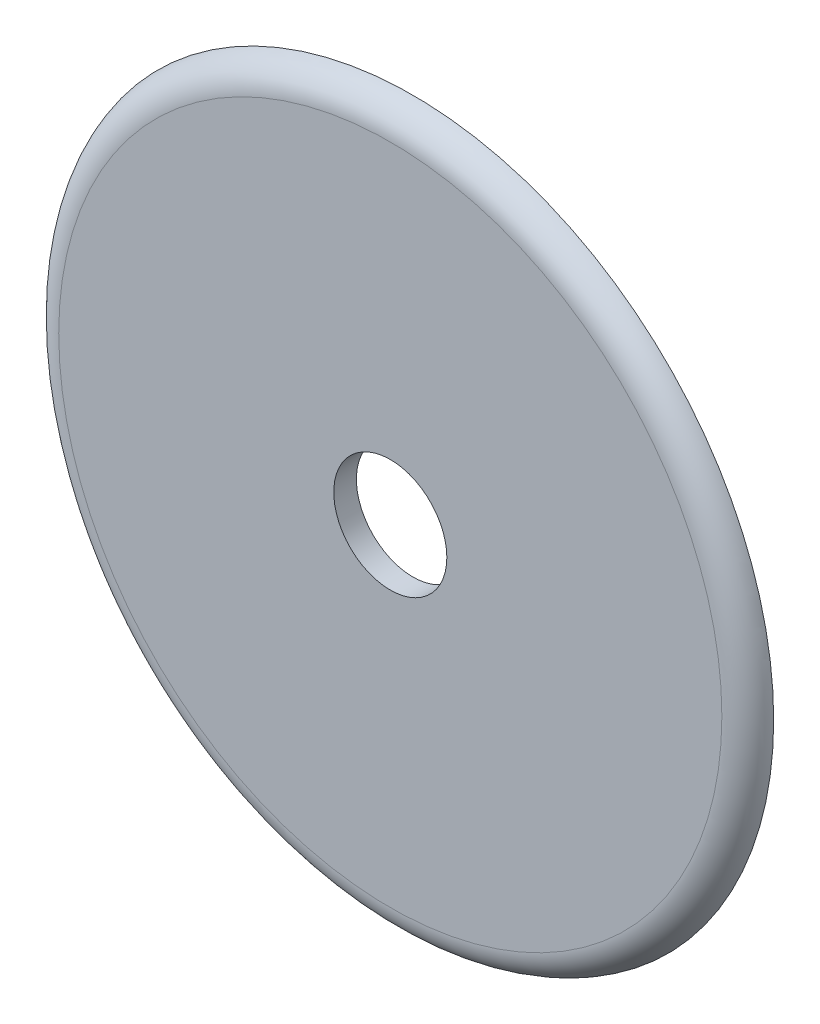
SolidWorks part; units mm, degrees
ref_plane "Front Plane" through (0, 0, 0) normal (0, 0, 1) x (1, 0, 0)
ref_plane "Top Plane" through (0, 0, 0) normal (0, 1, 0) x (1, 0, 0)
ref_plane "Right Plane" through (0, 0, 0) normal (1, 0, 0) x (0, 0, -1)
sketch "Sketch1" plane through (0, 0, 0) normal (0, 0, 1) x (1, 0, 0)
  circle A0 centre (0, 0) radius 47.85
  dimension "D1" = 95.7
extrude "Boss-Extrude1" add sketch "Sketch1" along normal blind 3
sketch "Sketch2" plane through (0, 0, 3) normal (0, 0, 1) x (1, 0, 0)
  circle A0 centre (0, 0) radius 7.5
  dimension "D1" = 15
extrude "Cut-Extrude1" cut sketch "Sketch2" against normal blind 6
fillet "Fillet2" radius 4 1 edges at (47.85, 0, 3)
